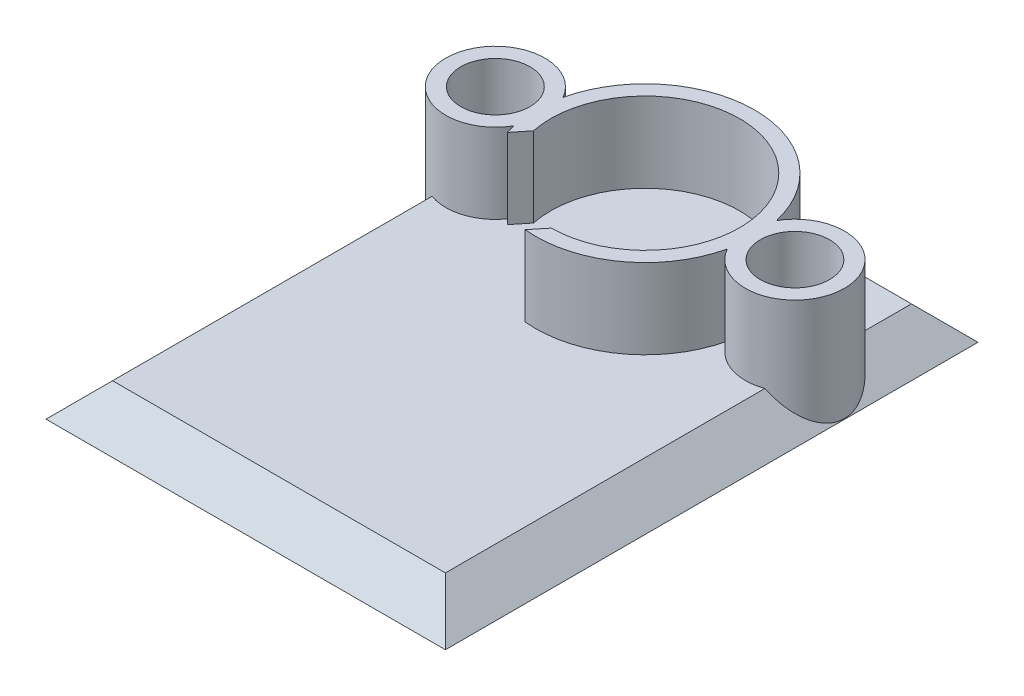
SolidWorks part; units mm, degrees
ref_plane "Front Plane" through (0, 0, 0) normal (0, 0, 1) x (1, 0, 0)
ref_plane "Top Plane" through (0, 0, 0) normal (0, 1, 0) x (1, 0, 0)
ref_plane "Right Plane" through (0, 0, 0) normal (1, 0, 0) x (0, 0, -1)
sketch "Sketch1" plane through (0, 0, 0) normal (0, 1, 0) x (1, 0, 0)
  line L0 (-22.5, 20) -> (22.5, 20) construction
  line L1 (-30, -40) -> (30, -40)
  line L2 (-30, -40) -> (-30, 40)
  line L3 (-30, 40) -> (30, 40)
  line L4 (30, -40) -> (30, 40)
  line L5 (-30, -40) -> (30, 40) construction
  line L6 (-30, 40) -> (30, -40) construction
  line L7 (0, 20) -> (0, 0) construction
  line L8 (-13.9045, 17.1181) -> (-15.6562, 14.9517)
  line L9 (-1.6595, 3.6339) -> (0.0922, 5.8003)
  line L10 (-14.7804, 16.0349) -> (-0.7837, 4.7171) construction
  line L11 (-7.782, 10.376) -> (0, 20)
  circle A0 centre (-22.5, 20) radius 5.2
  circle A1 centre (22.5, 20) radius 5.2
  circle A2 centre (0, 20) radius 14.2
  circle A3 centre (-22.5, 20) radius 7.45
  circle A4 centre (0, 20) radius 16.45
  circle A5 centre (22.5, 20) radius 7.45
  point P0 (0, 0)
  point P12 (0, 20)
  dimension "D3" = 10.4
  dimension "D4" = 28.4
  dimension "D1" = 60
  dimension "D2" = 80
  dimension "D5" = 45
  dimension "D6" = 20
  dimension "D10" = 18
  dimension "D7" = 2.25
  dimension "D8" = 2.25
  dimension "D9" = 2.25
extrude "Boss-Extrude2" add sketch "Sketch1" against normal blind 5 contours L3 L4 L1 L2
extrude "Boss-Extrude4" add sketch "Sketch1<7>" along normal blind 12 contours A4 A3 A0 | A5 A4 A3 A2 | A3 A4 | A4 A5 A1 | A4 A5 region at (-15.1376, 0, -16.3238) region at (-15.8031, 0, -20) region at (-29.7461, 0, -20) region at (15.8031, 0, -20) region at (16.5473, 0, -18.1183)
sketch "Sketch1<7>" plane through (0, 0, 0) normal (0, 1, 0) x (1, 0, 0) same geometry as "Sketch1"
chamfer "Chamfer1" distance 5 angle 45 4 edges at (0, 0, -40) (30, 0, 0) (0, 0, 40) (-30, 0, 0)
